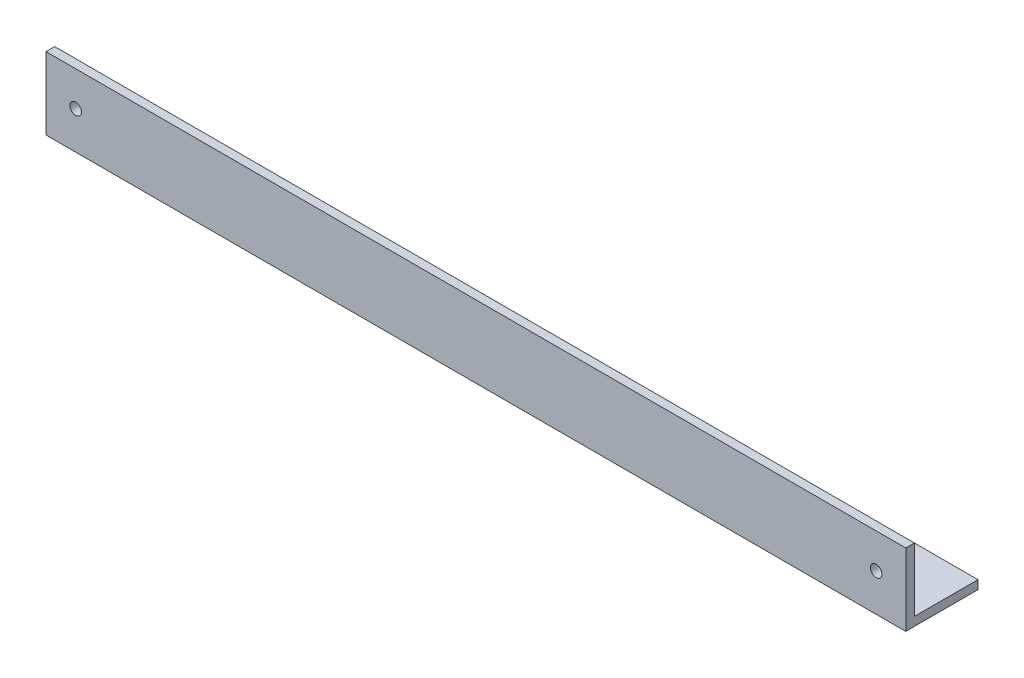
SolidWorks part; units mm, degrees
ref_plane "Спереди" through (0, 0, 0) normal (0, 0, 1) x (1, 0, 0)
ref_plane "Сверху" through (0, 0, 0) normal (0, 1, 0) x (1, 0, 0)
ref_plane "Справа" through (0, 0, 0) normal (1, 0, 0) x (0, 0, -1)
sketch "Эскиз1" plane through (0, 0, 0) normal (1, 0, 0) x (0, 0, -1)
  line L0 (0, 0) -> (50, 0)
  line L5 (0, 50) -> (0, 0)
extrude "Вытянуть-Тонкостенный2" add sketch "Эскиз1" along normal blind 595 thin thin type one direction reverse wall 6
sketch "Эскиз2" plane through (0, 0, 0) normal (0, 0, 1) x (1, 0, 0)
  line L0 (297.5, 50) -> (297.5, -14.5618) construction
  line L1 (595, 50) -> (0, 50) construction
  circle A0 centre (20.5, 26) radius 4
  circle A1 centre (574.5, 26) radius 4
extrude "Вырез-Вытянуть1" cut sketch "Эскиз2" against normal through all
